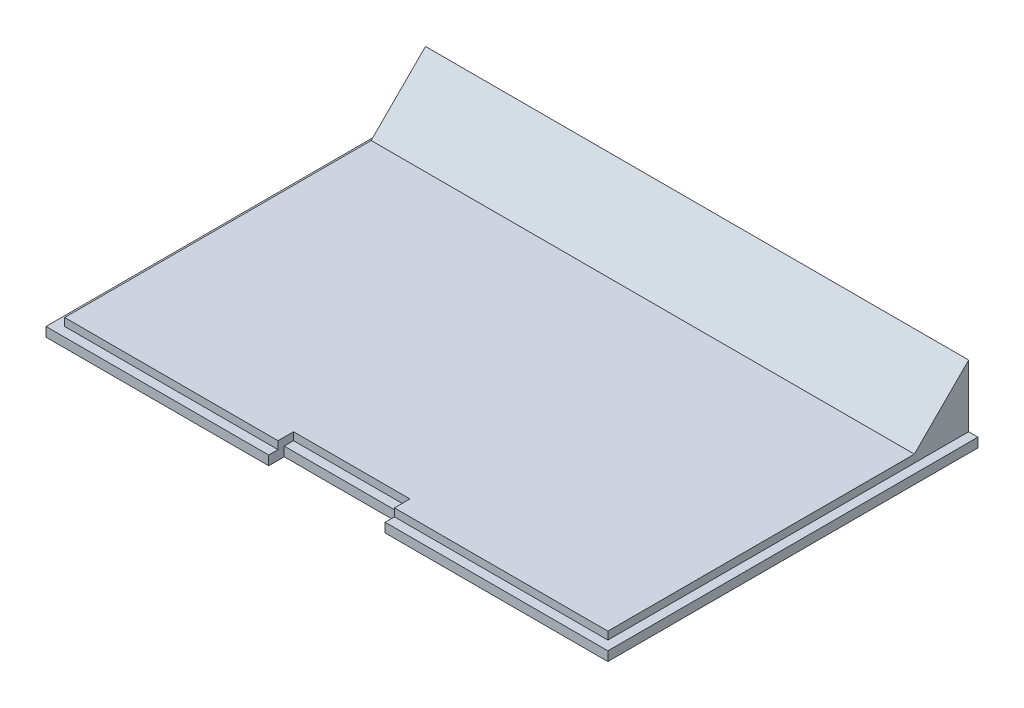
SolidWorks part; units mm, degrees
ref_plane "Přední rovina" through (0, 0, 0) normal (0, 0, 1) x (1, 0, 0)
ref_plane "Horní rovina" through (0, 0, 0) normal (0, 1, 0) x (1, 0, 0)
ref_plane "Pravá rovina" through (0, 0, 0) normal (1, 0, 0) x (0, 0, -1)
sketch "Skica2" plane through (0, 0, 0) normal (0, 1, 0) x (1, 0, 0)
  line L1 (0, 0) -> (72.4, 0)
  line L2 (0, 0) -> (0, 47.7)
  line L3 (0, 47.7) -> (72.4, 47.7)
  line L4 (72.4, 0) -> (72.4, 47.7)
  dimension "D1" = 47.7
  dimension "D2" = 72.4
extrude "Přidat vysunutím1" add sketch "Skica2" along normal blind 1.2
sketch "Skica3" plane through (0, 1.2, 0) normal (0, 1, 0) x (1, 0, 0)
  line L0 (72.4, 47.7) -> (0, 47.7) construction
  line L1 (1.2, 47.7) -> (71.2, 47.7)
  line L2 (1.2, 47.7) -> (1.2, 1.2)
  line L3 (1.2, 1.2) -> (71.2, 1.2)
  line L4 (71.2, 47.7) -> (71.2, 1.2)
  line L5 (0, 47.7) -> (0, 0) construction
  dimension "D1" = 46.5
  dimension "D2" = 70
  dimension "D3" = 1.2
extrude "Přidat vysunutím2" add sketch "Skica3" along normal blind 1
sketch "Skica4" plane through (0, 2.2, 0) normal (0, 1, 0) x (1, 0, 0)
  line L1 (71.2, 47.7) -> (1.2, 47.7)
  line L2 (71.2, 47.7) -> (71.2, 40.7)
  line L3 (71.2, 40.7) -> (1.2, 40.7)
  line L4 (1.2, 47.7) -> (1.2, 40.7)
  line L5 (1.2, 47.7) -> (1.2, 1.2) construction
  dimension "D1" = 7
  dimension "D2" = 70
extrude "Přidat vysunutím3" add sketch "Skica4" along normal blind 7
chamfer "Zkosení2" distance 7 angle 45 1 edges at (36.2, 9.2, -40.7)
sketch "Skica5" plane through (0, 2.2, 0) normal (0, 1, 0) x (1, 0, 0)
  line L0 (0, 0) -> (72.4, 0) construction
  line L1 (28.7, 0) -> (43.7, 0)
  line L2 (28.7, 0) -> (28.7, 2)
  line L3 (28.7, 2) -> (43.7, 2)
  line L4 (43.7, 0) -> (43.7, 2)
  line L5 (0, 47.7) -> (0, 0) construction
  dimension "D1" = 2
  dimension "D2" = 15
  dimension "D3" = 28.7
extrude "Odebrat vysunutím1" cut sketch "Skica5" against normal blind 10
sketch "Skica6" plane through (0, 2.2, 0) normal (0, 1, 0) x (1, 0, 0)
  line L1 (28.7, 2) -> (43.7, 2)
  line L2 (28.7, 2) -> (28.7, 3.2)
  line L3 (28.7, 3.2) -> (43.7, 3.2)
  line L4 (43.7, 2) -> (43.7, 3.2)
  dimension "D1" = 1.2
  dimension "D2" = 15
extrude "Odebrat vysunutím2" cut sketch "Skica6" against normal blind 1
